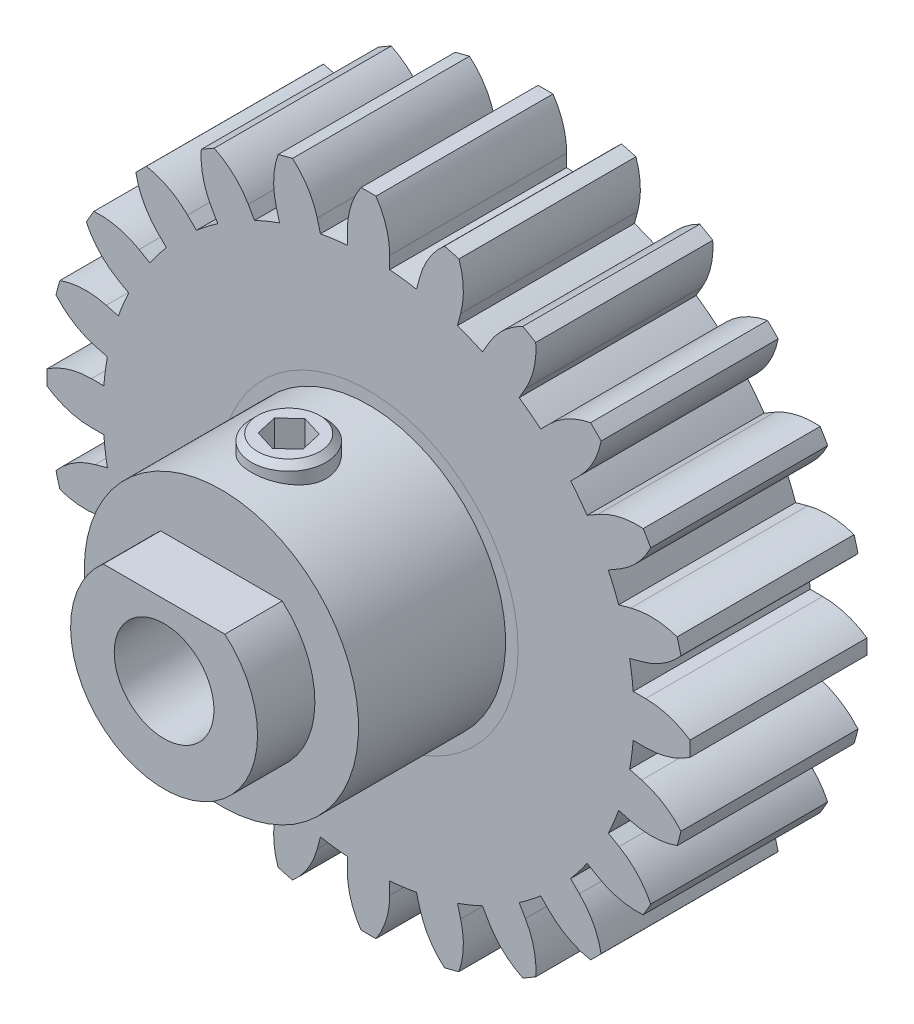
SolidWorks part; units mm, degrees
material "PA Type 6"
material "1060 Alloy"
material "Plain Carbon Steel"
material "PA Type 6"
ref_plane "Front Plane" through (0, 0, 0) normal (0, 0, 1) x (1, 0, 0)
ref_plane "Top Plane" through (0, 0, 0) normal (0, 1, 0) x (1, 0, 0)
ref_plane "Right Plane" through (0, 0, 0) normal (1, 0, 0) x (0, 0, -1)
ref_axis "Axis1" through (0, 0, -11.7513) along (0, 0, 1)
sketch "Sketch4" plane through (0, 0, 0) normal (0, 1, 0) x (1, 0, 0)
  line L0 (0, 23.226) -> (0, -37.2777) construction
  line L1 (2, 0.5) -> (2, -15.3)
  line L2 (2, -15.3) -> (3.75, -15.3)
  line L3 (3.75, -15.3) -> (3.75, -13)
  line L4 (3.75, -13) -> (5.5, -13)
  line L5 (5.5, -13) -> (5.5, -7.1)
  line L6 (5.5, -7.1) -> (6, -7.1)
  line L7 (6, -7.1) -> (6, 0)
  line L8 (6, 0) -> (5.5, 0)
  line L9 (5.5, 0) -> (5.5, 0.5)
  line L10 (5.5, 0.5) -> (2, 0.5)
  dimension "D1" = 4
  dimension "D2" = 11
  dimension "D3" = 12
  dimension "D4" = 7.5
  dimension "D5" = 0.5
  dimension "D6" = 7.1
  dimension "D7" = 15.8
  dimension "D8" = 13.5
revolve "Revolve1" add sketch "Sketch4" angle 360 about L0
sketch "Sketch5" plane through (0, 0, 0) normal (0, 1, 0) x (1, 0, 0)
  line L0 (0, 11.7513) -> (0, -13.6828) construction
  line L1 (-3.75, -15.3) -> (3.75, -15.3) construction
  circle A0 centre (0, -10.3) radius 1.25
  dimension "D2" = 2.5
  dimension "D1" = 5
extrude "Cut-Extrude1" cut sketch "Sketch5" along normal through all
sketch "Sketch6" plane through (0, 0, 13) normal (0, 0, 1) x (1, 0, 0)
  line L1 (2.4372, 4.65) -> (-2.4372, 4.65)
  line L2 (2.4372, 4.65) -> (2.4372, 2.85)
  line L3 (2.4372, 2.85) -> (-2.4372, 2.85)
  line L4 (-2.4372, 4.65) -> (-2.4372, 2.85)
  line L5 (2.4372, 4.65) -> (-2.4372, 2.85) construction
  line L6 (2.4372, 2.85) -> (-2.4372, 4.65) construction
  circle A0 centre (0, 0) radius 3.75 construction
  circle A1 centre (0, 0) radius 3.75 construction
  point P0 (0, 3.75)
  dimension "D1" = 6.6
extrude "Cut-Extrude2" cut sketch "Sketch6" along normal through all
sketch "Sketch1" plane through (0, 0, 0) normal (0, 0, 1) x (1, 0, 0)
  circle A0 centre (0, 0) radius 10.65
  circle A1 centre (0, 0) radius 6
  dimension "D1" = 21.3
  dimension "D2" = 12
extrude "Boss-Extrude1" add sketch "Sketch1" along normal blind 7.1 separate body
sketch "Sketch2" plane through (0, 0, 0) normal (0, 0, 1) x (1, 0, 0)
  line L0 (0, 19.1132) -> (0, -4.5821) construction
  line L1 (0.85, 10.616) -> (0.85, 11.116)
  line L2 (-0.85, 10.616) -> (-0.85, 11.116)
  line L3 (-0.85, 10.616) -> (0.85, 10.616)
  circle A0 centre (0, 0) radius 12.9 construction
  arc A1 (-0.3, 12.8965) -> (0.3, 12.8965) centre (0, 0) cw
  circle A2 centre (0, 0) radius 10.65 construction
  arc A3 (0.85, 11.116) -> (0.3, 12.8965) centre (-2.3069, 11.116) ccw
  arc A4 (-0.85, 11.116) -> (-0.3, 12.8965) centre (2.3069, 11.116) cw
  dimension "D1" = 25.8
  dimension "D2" = 0.6
  dimension "D3" = 1.7
  dimension "D4" = 0.5
extrude "Boss-Extrude2" add sketch "Sketch2" along normal up to surface (7.1 mm away) contours A3 A1 A4 L2 L3 L1 up to face at (10.65, 0, 7.1)
pattern_circular "CirPattern1" count 24 over 360 about axis through (0, 0, -11.7513) along (0, 0, 1) of "Boss-Extrude2"
ref_plane "Plane1" through (0, 1.5, 0) normal (0, 1, 0) x (1, 0, 0)
sketch "Sketch7" plane through (0, 1.5, 0) normal (0, 1, 0) x (1, 0, 0)
  circle A0 centre (0, -10.3) radius 1.5
  dimension "D1" = 3
extrude "Boss-Extrude3" add sketch "Sketch7" along normal blind 4.6 separate body
chamfer "Chamfer1" distance 0.25 angle 45 1 edges at (0, 6.1, 11.8)
sketch "Sketch8" plane through (0, 6.1, 0) normal (0, 1, 0) x (1, 0, 0)
  line L1 (0.1906, -11.1448) -> (0.8269, -10.5574)
  line L2 (0.8269, -10.5574) -> (0.6363, -9.7126)
  line L3 (0.6363, -9.7126) -> (-0.1906, -9.4552)
  line L4 (-0.1906, -9.4552) -> (-0.8269, -10.0426)
  line L5 (-0.8269, -10.0426) -> (-0.6363, -10.8874)
  line L6 (-0.6363, -10.8874) -> (0.1906, -11.1448)
  circle A0 centre (0, -10.3) radius 0.75 construction
  dimension "D1" = 1.5
extrude "Cut-Extrude3" cut sketch "Sketch8" against normal blind 2
